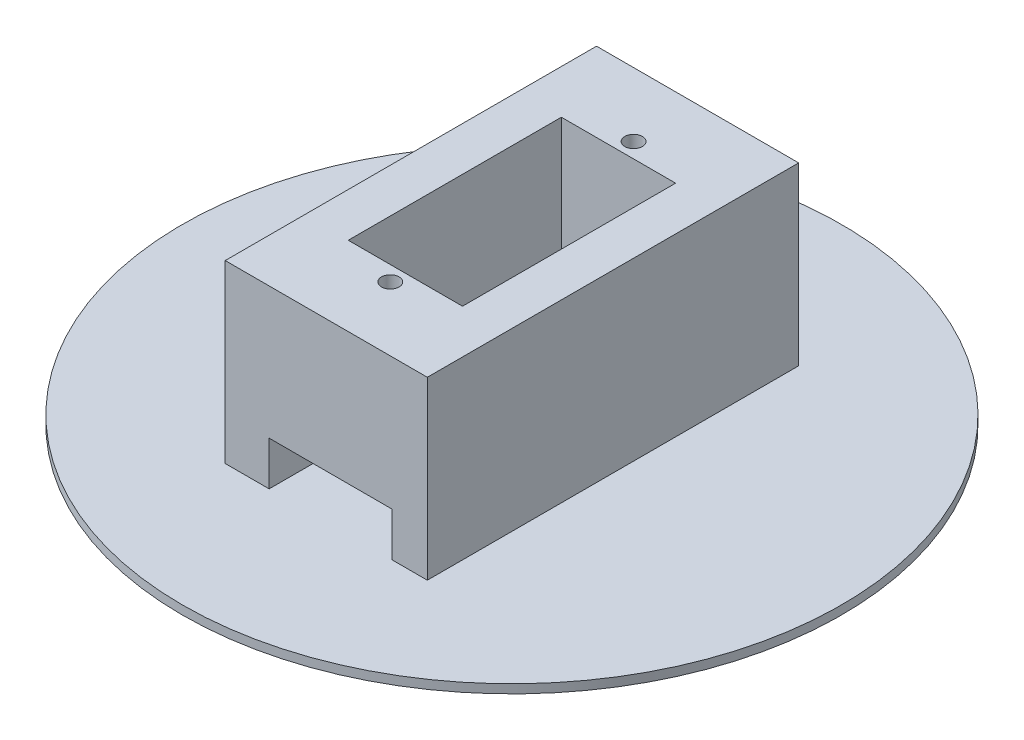
SolidWorks part; units mm, degrees
ref_plane "Front Plane" through (0, 0, 0) normal (0, 0, 1) x (1, 0, 0)
ref_plane "Top Plane" through (0, 0, 0) normal (0, 1, 0) x (1, 0, 0)
ref_plane "Right Plane" through (0, 0, 0) normal (1, 0, 0) x (0, 0, -1)
sketch "Sketch2" plane through (0, 0, 0) normal (0, 1, 0) x (1, 0, 0)
  line L0 (0, 16.125) -> (13, 16.125) construction
  line L1 (0, 0) -> (13, 0)
  line L2 (0, 0) -> (0, 32.25)
  line L3 (0, 32.25) -> (13, 32.25)
  line L4 (13, 0) -> (13, 32.25)
  line L5 (6.5, 0) -> (6.5, 32.25) construction
  line L6 (-5, -5) -> (18, -5)
  line L7 (18, -5) -> (18, 37.25)
  line L8 (-5, 37.25) -> (18, 37.25)
  line L9 (-5, -5) -> (-5, 37.25)
  line L10 (6.5, 32.25) -> (6.5, 29.964)
  line L11 (6.5, 32.25) -> (6.5, 28.25)
  line L12 (13, 28.25) -> (0, 28.25)
  line L13 (6.5, 0) -> (6.5, 2.286)
  line L14 (6.5, 0) -> (6.5, 4)
  line L15 (13, 4) -> (0, 4)
  circle A0 centre (6.5, 16.125) radius 37.5
  circle A1 centre (6.5, 29.964) radius 1
  circle A2 centre (6.5, 2.286) radius 1
  point P21 (6.5, 28.25)
  point P27 (6.5, 4)
  dimension "D5" = 2
  dimension "D8" = 2
  dimension "D10" = 75
  dimension "D1" = 13
  dimension "D2" = 32.25
  dimension "D4" = 2.286
  dimension "D6" = 4
  dimension "D7" = 2.286
  dimension "D9" = 4
  dimension "D3" = 5
extrude "Boss-Extrude1" add sketch "Sketch2" along normal blind 20 contours A2 L14 L15 L2 L1 L13 | A2 L13 L1 L4 L15 L14 | L9 L6 L7 L8 L4 L1 L2 L3 | A1 L11 L12 L4 L3 L10 | A1 L10 L3 L2 L12 L11 region at (3.0683, 0, -1.9816) region at (9.9317, 0, -1.9816) region at (3.0683, 0, -30.2684) region at (9.9317, 0, -30.2684) region at (-4.519, 0, -16.125)
extrude "Boss-Extrude2" add sketch "Sketch2<3>" against normal blind 1 contours L15 L4 L12 L2 | L9 L6 L7 L8 L4 L1 L2 L3 | A0 L6 L9 L8 L7 | A1 L11 L12 L4 L3 L10 | L11 A1 | A1 L10 L3 L2 L12 L11 | L11 A1 | A2 L13 L1 L4 L15 L14 | A2 L14 L15 L2 L1 L13 | L14 A2 | A2 region at (3.0683, 0, -1.9816) region at (9.9317, 0, -1.9816) region at (6.5, 0, -16.125) region at (6.0756, 0, -2.286) region at (3.0683, 0, -30.2684) region at (9.9317, 0, -30.2684) region at (6.0756, 0, -29.964) region at (6.9244, 0, -29.964) region at (-4.519, 0, -16.125) region at (-29.9393, 0, -16.125)
sketch "Sketch2<3>" plane through (0, 0, 0) normal (0, 1, 0) x (1, 0, 0) same geometry as "Sketch2"
sketch "Sketch4" plane through (0, 0, -37.25) normal (0, 0, -1) x (-1, 0, 0)
  line L1 (0, 0) -> (-14, 0)
  line L2 (0, 0) -> (0, 5)
  line L3 (0, 5) -> (-14, 5)
  line L4 (-14, 0) -> (-14, 5)
  dimension "D1" = 5
  dimension "D2" = 14
extrude "Cut-Extrude1" cut sketch "Sketch4" against normal blind 168
